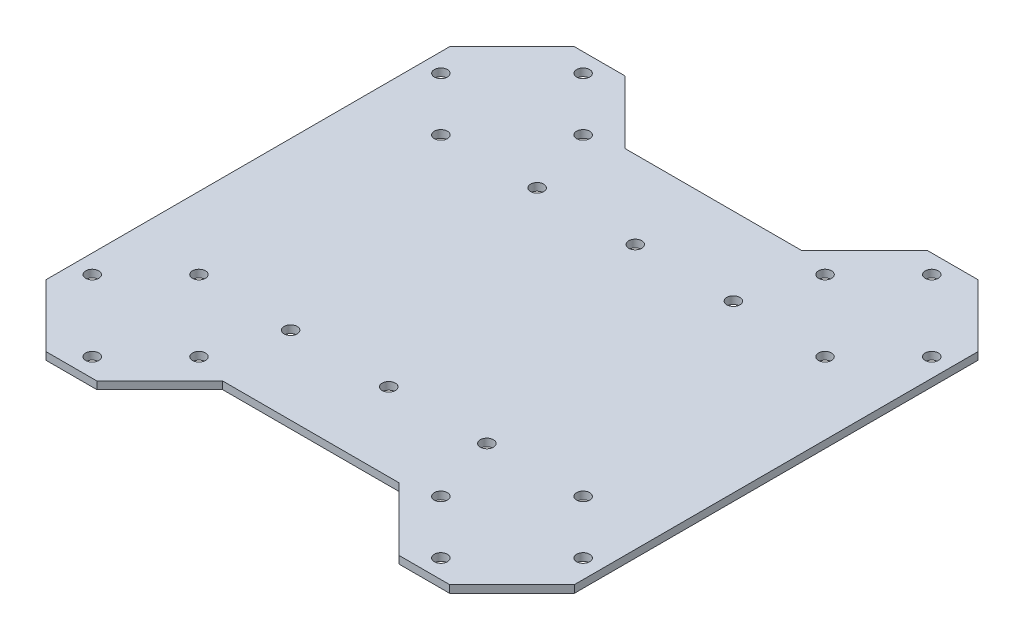
SolidWorks part; units mm, degrees
material "3k Carbon Fiber"
ref_plane "Front Plane" through (0, 0, 0) normal (0, 0, 1) x (1, 0, 0)
ref_plane "Top Plane" through (0, 0, 0) normal (0, 1, 0) x (1, 0, 0)
ref_plane "Right Plane" through (0, 0, 0) normal (1, 0, 0) x (0, 0, -1)
sketch "Sketch1" plane through (0, 0, 0) normal (0, 1, 0) x (1, 0, 0)
  line L0 (-59.3167, 108.2255) -> (101.1858, 108.2255)
  line L1 (101.1858, 108.2255) -> (125.9346, 83.4768)
  line L2 (125.9346, 83.4768) -> (125.9346, -77.0258)
  line L3 (125.9346, -77.0258) -> (101.1858, -101.7745)
  line L4 (101.1858, -101.7745) -> (-59.3167, -101.7745)
  line L5 (-59.3167, -101.7745) -> (-84.0654, -77.0258)
  line L6 (-84.0654, -77.0258) -> (-84.0654, 83.4768)
  line L7 (-84.0654, 83.4768) -> (-59.3167, 108.2255)
  dimension "D1" = 210
  dimension "D2" = 135
  dimension "D3" = 135
  dimension "D4" = 35
extrude "Boss-Extrude1" add sketch "Sketch1" along normal blind 3
sketch "Sketch2" plane through (0, 3, 0) normal (0, 1, 0) x (1, 0, 0)
  line L0 (-84.0654, -77.0258) -> (-45.1746, -38.1349)
  line L1 (-45.1746, -38.1349) -> (-20.4258, -62.8836)
  line L2 (-20.4258, -62.8836) -> (-59.3167, -101.7745)
  line L3 (125.9346, -77.0258) -> (93.8808, -37.1048)
  line L4 (93.8808, -37.1048) -> (66.7511, -58.8881)
  line L5 (66.7511, -58.8881) -> (101.1858, -101.7745)
  line L6 (101.1858, 108.2255) -> (62.1611, 69.9555)
  line L7 (62.1611, 69.9555) -> (86.6658, 44.9675)
  line L8 (86.6658, 44.9675) -> (125.9346, 83.4768)
  line L9 (-59.3167, 108.2255) -> (-24.1003, 65.9786)
  line L10 (-24.1003, 65.9786) -> (-50.8746, 43.6598)
  line L11 (-50.8746, 43.6598) -> (-84.0654, 83.4768)
  line L12 (-84.0654, -77.0258) -> (-59.3167, -101.7745)
  line L13 (101.1858, -101.7745) -> (125.9346, -77.0258)
  line L14 (101.1858, 108.2255) -> (125.9346, 83.4768)
  line L15 (-84.0654, 83.4768) -> (-59.3167, 108.2255)
  dimension "D1" = 55
  dimension "D2" = 90
  dimension "D3" = 55
  dimension "D4" = 90
  dimension "D5" = 55
  dimension "D6" = 90
  dimension "D7" = 90
  dimension "D8" = 55
  dimension "D9" = 90
extrude "Boss-Extrude2" add sketch "Sketch2" against normal blind 2
sketch "Sketch3" plane through (0, 3, 0) normal (0, 1, 0) x (1, 0, 0)
  line L0 (-41.2855, 65.4455) -> (-71.6911, 95.8511) construction
  line L1 (-59.3167, 108.2255) -> (-84.0654, 83.4768) construction
  line L2 (20.9346, 108.2255) -> (20.9346, -101.7745) construction
  line L3 (101.1858, 108.2255) -> (-59.3167, 108.2255) construction
  line L4 (-59.3167, -101.7745) -> (101.1858, -101.7745) construction
  line L5 (-84.0654, 3.2255) -> (125.9346, 3.2255) construction
  line L6 (-84.0654, 83.4768) -> (-84.0654, -77.0258) construction
  line L7 (125.9346, -77.0258) -> (125.9346, 83.4768) construction
  line L11 (-50.195, 98.9624) -> (-48.3565, 100.8009) construction
  line L12 (-48.3565, 100.8009) -> (-27.1433, 79.5877) construction
  line L13 (-27.1433, 79.5877) -> (-55.4276, 51.3034) construction
  line L14 (-55.4276, 51.3034) -> (-76.6408, 72.5166) construction
  circle A9 centre (-27.1433, 79.5877) radius 2.6
  circle A10 centre (-55.4276, 51.3034) radius 2.6
  circle A11 centre (-76.6408, 72.5166) radius 2.6
  circle A16 centre (-48.3565, 100.8009) radius 2.6
  circle A18 centre (118.51, 72.5166) radius 2.6
  circle A19 centre (97.2968, 51.3034) radius 2.6
  circle A20 centre (69.0125, 79.5877) radius 2.6
  circle A21 centre (90.2257, 100.8009) radius 2.6
  circle A22 centre (-55.4276, -44.8524) radius 2.6
  circle A23 centre (-76.6408, -66.0656) radius 2.6
  circle A24 centre (-48.3565, -94.3499) radius 2.6
  circle A25 centre (-27.1433, -73.1367) radius 2.6
  circle A26 centre (118.51, -66.0656) radius 2.6
  circle A27 centre (97.2968, -44.8524) radius 2.6
  circle A28 centre (90.2257, -94.3499) radius 2.6
  circle A29 centre (69.0125, -73.1367) radius 2.6
  dimension "D3" = 5.2
  dimension "D2" = 43
  dimension "D12" = 2.6
  dimension "D13" = 30
  dimension "D14" = 40
  dimension "D15" = 30
sketch "Sketch6" plane through (0, 3, 0) normal (0, 1, 0) x (1, 0, 0)
  line L0 (20.9346, 108.2255) -> (20.9346, -101.7745) construction
  line L1 (101.1858, 108.2255) -> (-59.3167, 108.2255) construction
  line L2 (-59.3167, -101.7745) -> (101.1858, -101.7745) construction
  line L3 (-18.0654, -45.7745) -> (-18.0654, -48.3745) construction
  line L10 (-18.0654, -45.7745) -> (59.9346, -45.7745)
  line L11 (-18.0654, -45.7745) -> (-18.0654, 52.2255)
  line L12 (-18.0654, 52.2255) -> (59.9346, 52.2255)
  line L13 (59.9346, -45.7745) -> (59.9346, 52.2255)
  line L14 (-18.0654, -45.7745) -> (59.9346, 52.2255) construction
  line L15 (-18.0654, 52.2255) -> (59.9346, -45.7745) construction
  circle A0 centre (-18.0654, 52.2255) radius 2.6
  circle A1 centre (59.9346, 52.2255) radius 2.6
  circle A2 centre (59.9346, -45.7745) radius 2.6
  circle A3 centre (-18.0654, -45.7745) radius 2.6
  circle A14 centre (20.9346, -45.7745) radius 2.6
  circle A15 centre (20.9346, 52.2255) radius 2.6
  point P6 (20.9346, 3.2255)
  dimension "D3" = 5.2
  dimension "D1" = 98
  dimension "D2" = 78
extrude "Cut-Extrude6" cut sketch "Sketch6" against normal through all contours A2 | A14 | A3 | A0 | A15 | A1
extrude "Cut-Extrude7" cut sketch "Sketch3" against normal through all contours A11 | A10 | A9 | A16 | A20 | A21 | A18 | A19 | A29 | A27 | A26 | A28 | A23 | A22 | A25 | A24
sketch "Sketch7" plane through (0, 3, 0) normal (0, 1, 0) x (1, 0, 0)
  line L0 (20.9346, 108.2255) -> (20.9346, 83.2255) construction
  line L1 (101.1858, 108.2255) -> (-59.3167, 108.2255) construction
  line L2 (-14.0654, 83.2255) -> (55.9346, 83.2255)
  line L3 (-14.0654, 83.2255) -> (-39.0654, 108.2255)
  line L4 (55.9346, 83.2255) -> (80.9346, 108.2255)
  line L5 (-39.0654, 108.2255) -> (80.9346, 108.2255)
  line L6 (-84.0654, 3.2255) -> (125.9346, 3.2255) construction
  line L7 (-84.0654, 83.4768) -> (-84.0654, -77.0258) construction
  line L8 (125.9346, -77.0258) -> (125.9346, 83.4768) construction
  line L9 (-14.0654, -76.7745) -> (-39.0654, -101.7745)
  line L10 (-14.0654, -76.7745) -> (55.9346, -76.7745)
  line L11 (55.9346, -76.7745) -> (80.9346, -101.7745)
  line L12 (-39.0654, -101.7745) -> (80.9346, -101.7745)
  point P7 (20.9346, 83.2255)
  dimension "D1" = 25
  dimension "D2" = 70
  dimension "D3" = 135
extrude "Cut-Extrude8" cut sketch "Sketch7" against normal through all contours L5 L4 L2 L3 | L9 L12 L11 L10
